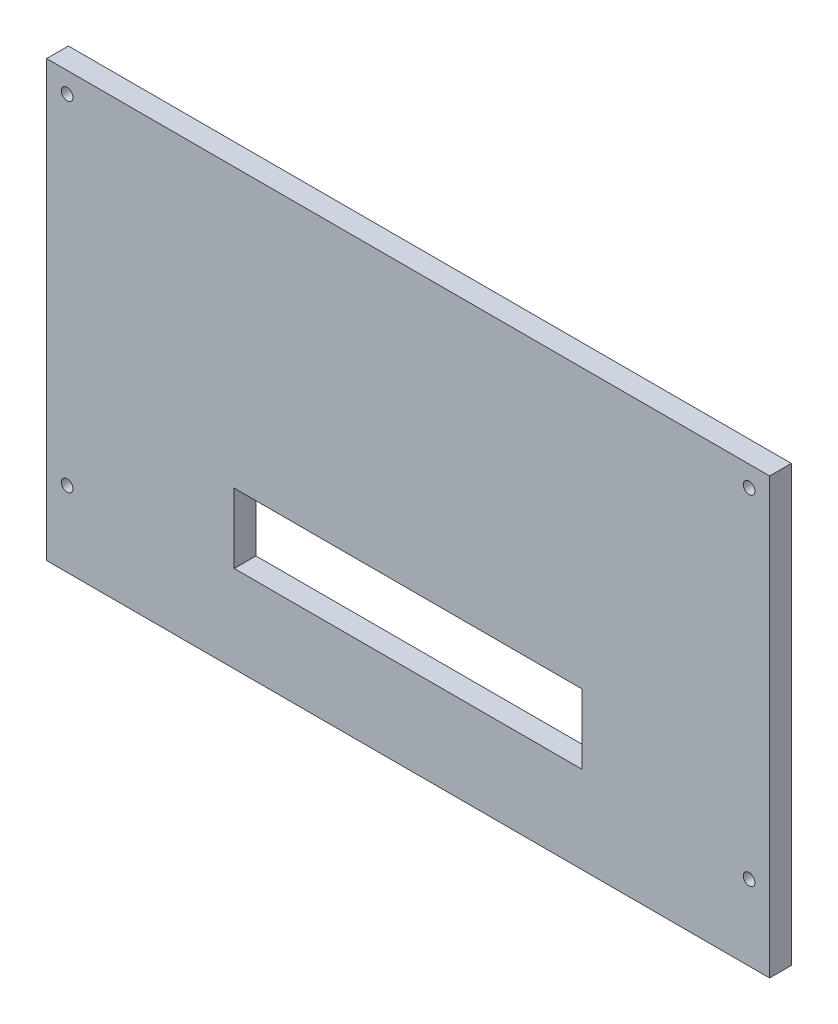
SolidWorks part; units mm, degrees
material "Acrylic (Medium-high impact)"
ref_plane "Front Plane" through (0, 0, 0) normal (0, 0, 1) x (1, 0, 0)
ref_plane "Top Plane" through (0, 0, 0) normal (0, 1, 0) x (1, 0, 0)
ref_plane "Right Plane" through (0, 0, 0) normal (1, 0, 0) x (0, 0, -1)
sketch "Sketch1" plane through (0, 0, 0) normal (0, 0, 1) x (1, 0, 0)
  line L1 (211.1756, 127) -> (0, 127)
  line L2 (211.1756, 127) -> (211.1756, 0)
  line L3 (211.1756, 0) -> (0, 0)
  line L4 (0, 127) -> (0, 0)
  line L5 (211.1756, 127) -> (0, 0) construction
  line L6 (211.1756, 0) -> (0, 127) construction
  point P0 (105.5878, 63.5)
  dimension "D1" = 127
  dimension "D2" = 211.1756
extrude "Boss-Extrude1" add sketch "Sketch1" along normal blind 6.35
hole_wizard "M3 Clearance Hole1" positions "Sketch2" profile "Sketch3" hole size "M3" standard "ANSI Metric" end condition through all
sketch "Sketch2" plane through (0, 0, 6.35) normal (0, 0, 1) x (1, 0, 0)
  line L0 (0, 127) -> (0, 0) construction
  line L1 (211.1756, 127) -> (0, 127) construction
  line L2 (211.1756, 0) -> (211.1756, 127) construction
  line L3 (0, 0) -> (211.1756, 0) construction
  point P0 (5.9944, 121.0056)
  point P2 (5.9944, 21.9964)
  point P4 (205.1812, 21.9964)
  point P6 (205.1812, 121.0056)
  dimension "D1" = 5.9944
  dimension "D2" = 5.9944
  dimension "D3" = 5.9944
  dimension "D4" = 21.9964
sketch "Sketch3" plane through (5.9944, 121.0056, 6.35) normal (1, 0, 0) x (0, -1, 0)
  line L0 (0, 0) -> (0, 6.35)
  line L1 (0, 6.35) -> (1.7, 6.35)
  line L2 (1.7, 6.35) -> (1.7, 0)
  line L5 (1.7, 0) -> (0, 0)
  line L11 (0, -6.35) -> (0, 107.95) construction
  dimension "Thru Hole Dia." = 3.4
  dimension "Thru Hole Depth" = 6.35
sketch "Sketch4" plane through (0, 0, 6.35) normal (0, 0, 1) x (1, 0, 0)
  line L0 (0, 127) -> (0, 0) construction
  line L1 (46.99, 107.95) -> (50.4952, 107.95)
  line L2 (46.99, 107.95) -> (46.99, 44.45)
  line L3 (46.99, 44.45) -> (50.4952, 44.45)
  line L4 (50.4952, 107.95) -> (50.4952, 44.45)
  line L5 (160.6804, 107.95) -> (164.1856, 107.95)
  line L6 (160.6804, 107.95) -> (160.6804, 44.45)
  line L7 (160.6804, 44.45) -> (164.1856, 44.45)
  line L8 (164.1856, 107.95) -> (164.1856, 44.45)
  line L9 (211.1756, 0) -> (211.1756, 127) construction
  line L10 (211.1756, 127) -> (0, 127) construction
  dimension "D1" = 3.5052
  dimension "D2" = 63.5
  dimension "D3" = 46.99
  dimension "D4" = 46.99
  dimension "D5" = 19.05
extrude "Cut-Extrude1" [suppressed] cut sketch "Sketch4" against normal through all
sketch "Sketch5" plane through (0, 0, 6.35) normal (0, 0, 1) x (1, 0, 0)
  line L0 (0, 36.1092) -> (76.2, 25.4)
  line L1 (0, 127) -> (0, 0) construction
  line L2 (76.2, 25.4) -> (134.9756, 25.4)
  line L3 (134.9756, 25.4) -> (211.1756, 36.1092)
  line L4 (211.1756, 0) -> (211.1756, 127) construction
  line L5 (211.1756, 36.1092) -> (211.1756, 0)
  line L6 (211.1756, 0) -> (0, 0)
  line L7 (0, 0) -> (0, 36.1092)
  dimension "D1" = 8
  dimension "D2" = 8
  dimension "D3" = 76.2
  dimension "D4" = 76.2
  dimension "D5" = 25.4
extrude "Cut-Extrude2" [suppressed] cut sketch "Sketch5" against normal through all
sketch "Sketch7" plane through (0, 0, 6.35) normal (0, 0, 1) x (1, 0, 0)
  line L0 (0, 0) -> (211.1756, 0) construction
  line L1 (54.7878, 45.72) -> (156.3878, 45.72)
  line L2 (54.7878, 45.72) -> (54.7878, 25.4)
  line L3 (54.7878, 25.4) -> (156.3878, 25.4)
  line L4 (156.3878, 45.72) -> (156.3878, 25.4)
  line L5 (54.7878, 45.72) -> (156.3878, 25.4) construction
  line L6 (54.7878, 25.4) -> (156.3878, 45.72) construction
  point P0 (105.5878, 35.56)
  point P5 (105.5878, 0)
  dimension "D1" = 20.32
  dimension "D2" = 101.6
  dimension "D3" = 25.4
extrude "tubingslot" cut sketch "Sketch7" against normal through all
